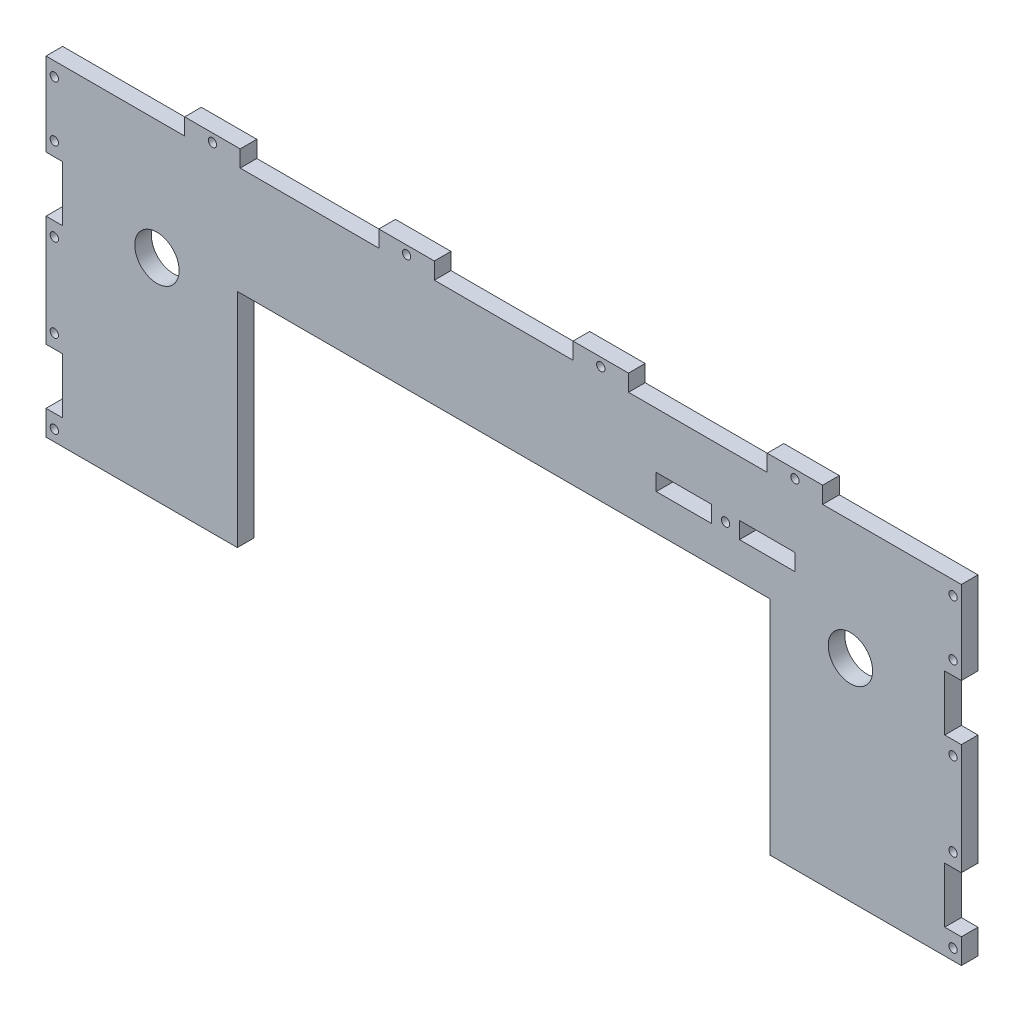
SolidWorks part; units mm, degrees
ref_plane "Plan de face" through (0, 0, 0) normal (0, 0, 1) x (1, 0, 0)
ref_plane "Plan de dessus" through (0, 0, 0) normal (0, 1, 0) x (1, 0, 0)
ref_plane "Plan de droite" through (0, 0, 0) normal (1, 0, 0) x (0, 0, -1)
sketch "Esquisse1" plane through (0, 0, 0) normal (0, 0, 1) x (1, 0, 0)
  line L0 (97.3951, 0) -> (-118.5049, 0) construction
  line L1 (-165, 119) -> (165, 119)
  line L2 (-165, 119) -> (-165, -119)
  line L3 (-165, -119) -> (165, -119)
  line L4 (165, 119) -> (165, -119)
  line L5 (0, 79.3588) -> (0, -79.3588) construction
  line L6 (-92.5, -55) -> (-77.5, -55)
  line L7 (-92.5, -55) -> (-92.5, -61)
  line L8 (-92.5, -61) -> (-77.5, -61)
  line L9 (-77.5, -55) -> (-77.5, -61)
  line L10 (-7.5, -55) -> (7.5, -55)
  line L11 (-7.5, -55) -> (-7.5, -61)
  line L12 (-7.5, -61) -> (7.5, -61)
  line L13 (7.5, -55) -> (7.5, -61)
  line L14 (77.5, -55) -> (92.5, -55)
  line L15 (77.5, -55) -> (77.5, -61)
  line L16 (77.5, -61) -> (92.5, -61)
  line L17 (92.5, -55) -> (92.5, -61)
  line L18 (-225.3679, 76) -> (203.1013, 76) construction
  line L19 (55, 99) -> (75, 99)
  line L20 (55, 99) -> (55, 93)
  line L21 (55, 93) -> (75, 93)
  line L22 (75, 99) -> (75, 93)
  line L23 (85, 99) -> (105, 99)
  line L24 (85, 99) -> (85, 93)
  line L25 (85, 93) -> (105, 93)
  line L26 (105, 99) -> (105, 93)
  circle A0 centre (-125, 76) radius 8
  circle A1 centre (125, 76) radius 8
  dimension "D23" = 16
  dimension "D24" = 16
  dimension "D1" = 238
  dimension "D2" = 330
  dimension "D3" = 165
  dimension "D4" = 119
  dimension "D5" = 15
  dimension "D6" = 6
  dimension "D7" = 6
  dimension "D8" = 15
  dimension "D9" = 6
  dimension "D10" = 15
  dimension "D11" = 70
  dimension "D12" = 70
  dimension "D13" = 58
  dimension "D14" = 72.5
  dimension "D15" = 6
  dimension "D16" = 20
  dimension "D17" = 20
  dimension "D18" = 6
  dimension "D19" = 10
  dimension "D20" = 60
  dimension "D21" = 20
  dimension "D22" = 20
  dimension "D25" = 40
  dimension "D26" = 40
  dimension "D27" = 195
extrude "Boss.-Extru.1" add sketch "Esquisse1" along normal blind 6
sketch "Esquisse2" plane through (0, 0, 6) normal (0, 0, 1) x (1, 0, 0)
  line L0 (243.146, 0) -> (-260.0003, 0) construction
  line L1 (0, 180.4713) -> (0, -129.6072) construction
  line L2 (165, 119) -> (-165, 119) construction
  line L3 (-115, 119) -> (-95, 119)
  line L4 (-115, 119) -> (-115, 125)
  line L5 (-115, 125) -> (-95, 125)
  line L6 (-95, 119) -> (-95, 125)
  line L7 (-165, 119) -> (-165, -119) construction
  line L8 (-45, 119) -> (-25, 119)
  line L9 (-45, 119) -> (-45, 125)
  line L10 (-45, 125) -> (-25, 125)
  line L11 (-25, 119) -> (-25, 125)
  line L12 (25, 119) -> (25, 125)
  line L13 (45, 125) -> (25, 125)
  line L14 (45, 119) -> (45, 125)
  line L15 (45, 119) -> (25, 119)
  line L16 (95, 119) -> (95, 125)
  line L17 (115, 125) -> (95, 125)
  line L18 (115, 119) -> (115, 125)
  line L19 (115, 119) -> (95, 119)
  line L20 (-115, 119) -> (-95, 119)
  line L21 (-115, 119) -> (-115, 125)
  line L22 (-115, 125) -> (-95, 125)
  line L23 (-95, 119) -> (-95, 125)
  line L24 (-45, 119) -> (-25, 119)
  line L25 (-45, 119) -> (-45, 125)
  line L26 (-45, 125) -> (-25, 125)
  line L27 (-25, 119) -> (-25, 125)
  line L28 (25, 119) -> (25, 125)
  line L29 (45, 125) -> (25, 125)
  line L30 (45, 119) -> (45, 125)
  line L31 (45, 119) -> (25, 119)
  line L32 (95, 119) -> (95, 125)
  line L33 (115, 125) -> (95, 125)
  line L34 (115, 119) -> (115, 125)
  line L35 (115, 119) -> (95, 119)
  line L36 (115, -119) -> (95, -119)
  line L37 (115, -119) -> (115, -125)
  line L38 (115, -125) -> (95, -125)
  line L39 (95, -119) -> (95, -125)
  line L40 (45, -119) -> (25, -119)
  line L41 (45, -119) -> (45, -125)
  line L42 (45, -125) -> (25, -125)
  line L43 (25, -119) -> (25, -125)
  line L44 (-25, -119) -> (-25, -125)
  line L45 (-45, -125) -> (-25, -125)
  line L46 (-45, -119) -> (-45, -125)
  line L47 (-45, -119) -> (-25, -119)
  line L48 (-95, -119) -> (-95, -125)
  line L49 (-115, -125) -> (-95, -125)
  line L50 (-115, -119) -> (-115, -125)
  line L51 (-115, -119) -> (-95, -119)
  line L52 (115, -119) -> (95, -119)
  line L53 (115, -119) -> (115, -125)
  line L54 (115, -125) -> (95, -125)
  line L55 (95, -119) -> (95, -125)
  line L56 (45, -119) -> (25, -119)
  line L57 (45, -119) -> (45, -125)
  line L58 (45, -125) -> (25, -125)
  line L59 (25, -119) -> (25, -125)
  line L60 (-25, -119) -> (-25, -125)
  line L61 (-45, -125) -> (-25, -125)
  line L62 (-45, -119) -> (-45, -125)
  line L63 (-45, -119) -> (-25, -119)
  line L64 (-95, -119) -> (-95, -125)
  line L65 (-115, -125) -> (-95, -125)
  line L66 (-115, -119) -> (-115, -125)
  line L67 (-115, -119) -> (-95, -119)
  line M9 (-165, -119) -> (165, -119)
  line M11 (165, 119) -> (-165, 119)
  dimension "D1" = 6
  dimension "D2" = 6
  dimension "D3" = 20
  dimension "D4" = 20
  dimension "D5" = 50
  dimension "D6" = 50
extrude "Boss.-Extru.2" add sketch "Esquisse2" against normal blind 6 contours L6 L5 L4 M11 | L11 L10 L9 M11 | L14 L13 L12 M11 | L18 L17 L16 M11 | L39 L38 L37 M9 | L43 L42 L41 M9 | L46 L45 L44 M9 | L50 L49 L48 M9 region at (-105, 122, 6) region at (105, 122, 6) region at (35, 122, 6) region at (-35, 122, 6) region at (105, -122, 6) region at (-105, -122, 6) region at (-35, -122, 6) region at (35, -122, 6)
sketch "Esquisse3" plane through (0, 0, 6) normal (0, 0, 1) x (1, 0, 0)
  line L0 (-165, 119) -> (-165, -119) construction
  line L1 (-165, 69) -> (-159, 69)
  line L2 (-165, 69) -> (-165, 89)
  line L3 (-165, 89) -> (-159, 89)
  line L4 (-159, 69) -> (-159, 89)
  line L5 (234.1368, 0) -> (-337.9213, 0) construction
  line L6 (-165, 29) -> (-159, 29)
  line L7 (-165, 29) -> (-165, 9)
  line L8 (-165, 9) -> (-159, 9)
  line L9 (-159, 29) -> (-159, 9)
  line L10 (0, 279.7488) -> (0, -188.1201) construction
  line L11 (-115, 119) -> (-165, 119) construction
  line L12 (-159, -29) -> (-159, -9)
  line L13 (-165, -9) -> (-159, -9)
  line L14 (-165, -29) -> (-165, -9)
  line L15 (-165, -29) -> (-159, -29)
  line L16 (-159, -69) -> (-159, -89)
  line L17 (-165, -89) -> (-159, -89)
  line L18 (-165, -69) -> (-165, -89)
  line L19 (-165, -69) -> (-159, -69)
  line L20 (165, -69) -> (159, -69)
  line L21 (165, -69) -> (165, -89)
  line L22 (165, -89) -> (159, -89)
  line L23 (159, -69) -> (159, -89)
  line L24 (165, -29) -> (159, -29)
  line L25 (165, -29) -> (165, -9)
  line L26 (165, -9) -> (159, -9)
  line L27 (159, -29) -> (159, -9)
  line L28 (159, 29) -> (159, 9)
  line L29 (165, 9) -> (159, 9)
  line L30 (165, 29) -> (165, 9)
  line L31 (165, 29) -> (159, 29)
  line L32 (159, 69) -> (159, 89)
  line L33 (165, 89) -> (159, 89)
  line L34 (165, 69) -> (165, 89)
  line L35 (165, 69) -> (159, 69)
  line L36 (153, -119) -> (153, -109)
  line L37 (-165, -119) -> (-153, -119)
  line L38 (-165, -119) -> (-165, -109)
  line L39 (-165, -109) -> (-153, -109)
  line L40 (-153, -119) -> (-153, -109)
  line L41 (165, -109) -> (153, -109)
  line L42 (165, -119) -> (165, -109)
  line L43 (165, -119) -> (153, -119)
  dimension "D1" = 40
  dimension "D2" = 6
  dimension "D3" = 6
  dimension "D4" = 20
  dimension "D5" = 20
  dimension "D6" = 30
  dimension "D7" = 12
  dimension "D8" = 10
extrude "Enlèv. mat.-Extru.1" cut sketch "Esquisse3" against normal blind 6
sketch "Esquisse4" plane through (0, 0, 6) normal (0, 0, 1) x (1, 0, 0)
  line L0 (-162, 122) -> (-162, -131.0602) construction
  line L1 (0, 158.5579) -> (0, -182.4489) construction
  line L2 (-115, 119) -> (-165, 119) construction
  line L3 (-106.4439, -58) -> (117.3944, -58) construction
  line L4 (-159, 89) -> (-165, 89) construction
  line L5 (-165, 119) -> (-165, 89) construction
  line L6 (-165, 69) -> (-159, 69) construction
  line L7 (-159, 29) -> (-165, 29) construction
  line L8 (-165, 9) -> (-159, 9) construction
  line L9 (-159, -9) -> (-165, -9) construction
  line L10 (-92.5, -55) -> (-92.5, -61) construction
  line L11 (-77.5, -61) -> (-77.5, -55) construction
  line L12 (-165, -29) -> (-159, -29) construction
  line L13 (-159, -69) -> (-165, -69) construction
  line L14 (-165, -89) -> (-159, -89) construction
  line L15 (-7.5, -55) -> (-7.5, -61) construction
  line L16 (162, 122) -> (162, -131.0602) construction
  line L17 (116.5184, 96) -> (43.4816, 96) construction
  line L18 (-126.5544, 122) -> (2.7821, 122) construction
  line L19 (-45, 119) -> (-95, 119) construction
  line L20 (-45, 119) -> (-45, 125) construction
  line L21 (75, 93) -> (75, 99) construction
  line L23 (55, 93) -> (75, 93) construction
  circle A0 centre (-162, 114) radius 1.5
  circle A1 centre (-162, 94) radius 1.5
  circle A2 centre (-162, 64) radius 1.5
  circle A3 centre (-162, 34) radius 1.5
  circle A4 centre (-162, 4) radius 1.5
  circle A5 centre (-105, 122) radius 1.5
  circle A6 centre (-162, -4) radius 1.5
  circle A7 centre (-162, -34) radius 1.5
  circle A8 centre (-162, -64) radius 1.5
  circle A9 centre (-162, -94) radius 1.5
  circle A10 centre (-97.5, -58) radius 1.5
  circle A11 centre (-72.5, -58) radius 1.5
  circle A12 centre (162, -94) radius 1.5
  circle A13 centre (162, -64) radius 1.5
  circle A14 centre (162, -34) radius 1.5
  circle A15 centre (162, -4) radius 1.5
  circle A16 centre (80, 96) radius 1.5
  circle A17 centre (162, 4) radius 1.5
  circle A18 centre (162, 34) radius 1.5
  circle A19 centre (162, 64) radius 1.5
  circle A20 centre (162, 94) radius 1.5
  circle A21 centre (162, 114) radius 1.5
  circle A22 centre (-12.5, -58) radius 1.5
  circle A23 centre (12.5, -58) radius 1.5
  circle A24 centre (72.5, -58) radius 1.5
  circle A25 centre (97.5, -58) radius 1.5
  circle A26 centre (-35, 122) radius 1.5
  circle A27 centre (35, 122) radius 1.5
  circle A28 centre (105, 122) radius 1.5
  dimension "D1" = 3
  dimension "D2" = 3
  dimension "D3" = 3
  dimension "D4" = 3
  dimension "D5" = 3
  dimension "D6" = 3
  dimension "D7" = 3
  dimension "D8" = 3
  dimension "D9" = 3
  dimension "D10" = 3
  dimension "D11" = 3
  dimension "D12" = 5
  dimension "D13" = 5
  dimension "D15" = 5
  dimension "D16" = 5
  dimension "D17" = 5
  dimension "D19" = 3
  dimension "D20" = 5
  dimension "D21" = 5
  dimension "D23" = 3
  dimension "D24" = 3
  dimension "D25" = 5
  dimension "D26" = 5
  dimension "D27" = 5
  dimension "D28" = 10
  dimension "D29" = 3
  dimension "D30" = 5
  dimension "D31" = 3
  dimension "D33" = 10
  dimension "D14" = 3
  dimension "D18" = 5
  dimension "D22" = 5
  dimension "D32" = 3
extrude "Enlèv. mat.-Extru.2" cut sketch "Esquisse4" against normal blind 6
sketch "Esquisse5" plane through (0, 0, 6) normal (0, 0, 1) x (1, 0, 0)
  line L1 (-200.0968, 0) -> (223.5072, 0)
  line L2 (-200.0968, 0) -> (-200.0968, -150.3561)
  line L3 (-200.0968, -150.3561) -> (223.5072, -150.3561)
  line L4 (223.5072, 0) -> (223.5072, -150.3561)
extrude "Enlèv. mat.-Extru.3" cut sketch "Esquisse5" against normal blind 6
sketch "Esquisse6" plane through (0, 0, 6) normal (0, 0, 1) x (1, 0, 0)
  line L0 (-165, 69) -> (-165, 29) construction
  line L2 (165, 0) -> (-165, 0) construction
  text T0 "SUDRIABOTIK" font "Century Gothic" height in points 72
  dimension "D1" = 83.5
  dimension "D2" = 29.5
extrude "Enlèv. mat.-Extru.4" cut sketch "Esquisse6" against normal blind 6
sketch "Esquisse7" plane through (0, 0, 6) normal (0, 0, 1) x (1, 0, 0)
  line L0 (-42.8696, 29.5) -> (-48.7731, 29.5) construction
  line L1 (-44.3875, 29.5) -> (-45.9701, 29.5)
  line L2 (-44.3875, 29.5) -> (-44.3875, 31.4538)
  line L3 (-44.3875, 31.4538) -> (-45.9701, 31.4538)
  line L4 (-45.9701, 29.5) -> (-45.9701, 31.4538)
  line L5 (-47.0635, 31.4538) -> (-44.8768, 31.4538) construction
  line L6 (-23.9531, 46.5962) -> (-27.525, 46.5962) construction
  line L7 (-45.1788, 46.5937) -> (-43.5909, 46.5937)
  line L8 (-45.1788, 46.5937) -> (-45.1788, 48.5305)
  line L9 (-45.1788, 48.5305) -> (-43.5909, 48.5305)
  line L10 (-43.5909, 46.5937) -> (-43.5909, 48.5305)
  line L11 (-26.3286, 46.5962) -> (-25.4223, 46.5962)
  line L12 (-26.3286, 46.5962) -> (-26.3286, 48.55)
  line L13 (-26.3286, 48.55) -> (-25.4223, 48.55)
  line L14 (-25.4223, 46.5962) -> (-25.4223, 48.55)
  line L15 (-27.525, 46.5962) -> (-27.525, 40.2462) construction
  line L16 (-27.525, 43.4212) -> (-29.2346, 43.4212)
  line L17 (-27.525, 43.4212) -> (-27.525, 42.4505)
  line L18 (-27.525, 42.4505) -> (-29.2346, 42.4505)
  line L19 (-29.2346, 43.4212) -> (-29.2346, 42.4505)
  line L20 (-29.2346, 29.5) -> (-29.2346, 48.55) construction
  line L21 (-2.2967, 37.5596) -> (4.5112, 37.5596) construction
  line L22 (0.6712, 37.5596) -> (1.8879, 37.5596)
  line L23 (0.6712, 37.5596) -> (0.6712, 35.6058)
  line L24 (0.6712, 35.6058) -> (1.8879, 35.6058)
  line L25 (1.8879, 37.5596) -> (1.8879, 35.6058)
  line L26 (5.4118, 35.6058) -> (-3.224, 35.6058) construction
  line L27 (15.2154, 46.5962) -> (15.2154, 40.4904) construction
  line L28 (15.2154, 43.5433) -> (13.5058, 43.5433)
  line L29 (15.2154, 43.5433) -> (15.2154, 40.4904)
  line L30 (15.2154, 40.4904) -> (13.5058, 40.4904)
  line L31 (13.5058, 43.5433) -> (13.5058, 40.4904)
  line L32 (13.5058, 29.5) -> (13.5058, 48.55) construction
  line L33 (15.2154, 38.5365) -> (15.2154, 31.4538) construction
  line L34 (15.2154, 32.964) -> (13.5058, 32.964)
  line L35 (15.2154, 32.964) -> (15.2154, 35.6058)
  line L36 (15.2154, 35.6058) -> (13.5058, 35.6058)
  line L37 (13.5058, 32.964) -> (13.5058, 35.6058)
  line L39 (29.3929, 39.4529) -> (27.6822, 39.4529)
  line L40 (29.3929, 39.4529) -> (29.3929, 38.5462)
  line L41 (29.3929, 38.5462) -> (27.6822, 38.5462)
  line L42 (27.6822, 39.4529) -> (27.6822, 38.5462)
  line L43 (45.9733, 39.5873) -> (47.6814, 39.5873)
  line L44 (45.9733, 39.5873) -> (45.9733, 38.4818)
  line L45 (45.9733, 38.4818) -> (47.6814, 38.4818)
  line L46 (47.6814, 39.5873) -> (47.6814, 38.4818)
  spline S0 degree 3 poles (-39.8701, 46.0619) (-40.0299, 46.1061) (-40.3695, 46.2) (-40.9238, 46.3025) (-41.5477, 46.3928) (-42.2438, 46.4694) (-43.0115, 46.5243) (-43.8512, 46.5655) (-44.7634, 46.5933) (-45.3958, 46.5952) (-45.724, 46.5962) knots 0 0 0 0 0.084319 0.179285 0.286583 0.405111 0.535593 0.67819 0.832976 1 1 1 1 construction
  spline S1 degree 3 poles (-44.9264, 48.55) (-44.5919, 48.5476) (-43.9455, 48.5429) (-43.0114, 48.5134) (-42.1472, 48.4612) (-41.3556, 48.3852) (-40.6345, 48.2918) (-39.986, 48.1748) (-39.4066, 48.0366) (-39.0502, 47.9188) (-38.8817, 47.8631) knots 0 0 0 0 0.164289 0.317406 0.458844 0.589367 0.707831 0.81577 0.91288 1 1 1 1 construction
  spline S2 degree 3 poles (37.6465, 47.0846) (37.4657, 47.0824) (37.1058, 47.078) (36.5709, 47.0202) (36.043, 46.9379) (35.522, 46.8204) (35.0101, 46.6604) (34.5026, 46.4762) (34.004, 46.2518) (33.516, 45.9983) (33.0429, 45.7178) (32.5966, 45.4077) (32.1757, 45.0754) (31.7814, 44.72) (31.4148, 44.3398) (31.0687, 43.9406) (30.757, 43.5108) (30.4714, 43.0623) (30.2157, 42.5955) (29.9884, 42.1154) (29.8024, 41.618) (29.6508, 41.1088) (29.5251, 40.5886) (29.4454, 40.0534) (29.387, 39.5058) (29.3829, 39.1358) (29.3808, 38.9487) knots 0 0 0 0 0.042023 0.083645 0.124984 0.166247 0.207702 0.249631 0.291742 0.334743 0.37746 0.419556 0.461044 0.502096 0.542891 0.583801 0.624864 0.666225 0.707399 0.748557 0.789655 0.83074 0.87207 0.913993 0.956498 1 1 1 1 construction
  spline S3 degree 3 poles (37.7151, 29.0115) (37.3699, 29.02) (36.6894, 29.0366) (35.6905, 29.1791) (34.731, 29.4019) (33.8138, 29.7204) (32.9384, 30.132) (32.1029, 30.6338) (31.3109, 31.2293) (30.5688, 31.9051) (29.8898, 32.6409) (29.2979, 33.4292) (28.7959, 34.2546) (28.3857, 35.1195) (28.0609, 36.0196) (27.8394, 36.9609) (27.6961, 37.9381) (27.6795, 38.6034) (27.6712, 38.941) knots 0 0 0 0 0.065819 0.129747 0.192072 0.253459 0.31457 0.37628 0.439026 0.503267 0.567493 0.629705 0.691 0.751452 0.812004 0.87315 0.935635 1 1 1 1 construction
  spline S4 degree 3 poles (45.9885, 39.0364) (45.9863, 39.221) (45.9819, 39.5872) (45.9246, 40.1286) (45.8424, 40.6579) (45.7239, 41.1732) (45.5713, 41.6744) (45.383, 42.1613) (45.161, 42.6355) (44.9062, 43.0959) (44.6199, 43.5378) (44.3069, 43.9601) (43.962, 44.3551) (43.595, 44.7325) (43.1968, 45.0842) (42.7691, 45.4104) (42.3171, 45.7188) (41.8385, 45.9971) (41.3446, 46.2541) (40.8378, 46.4743) (40.3238, 46.6613) (39.804, 46.8209) (39.274, 46.9374) (38.7373, 47.0203) (38.1947, 47.078) (37.8298, 47.0824) (37.6465, 47.0846) knots 0 0 0 0 0.042915 0.08513 0.126473 0.167453 0.207976 0.248249 0.28875 0.32967 0.370537 0.411129 0.451819 0.492406 0.533486 0.575263 0.617441 0.660672 0.70394 0.746868 0.789079 0.831104 0.873238 0.915166 0.957381 1 1 1 1 construction
  spline S5 degree 3 poles (47.6981, 39.0326) (47.6896, 38.69) (47.673, 38.0145) (47.5306, 37.0231) (47.3072, 36.0702) (46.9883, 35.1571) (46.5788, 34.2831) (46.0745, 33.4504) (45.4805, 32.6588) (44.8044, 31.9169) (44.0675, 31.2365) (43.277, 30.6437) (42.4508, 30.1336) (41.5783, 29.7265) (40.6709, 29.4012) (39.7207, 29.1794) (38.732, 29.0363) (38.0578, 29.0199) (37.7151, 29.0115) knots 0 0 0 0 0.065227 0.128569 0.19032 0.251378 0.312388 0.373789 0.436431 0.500567 0.564687 0.627136 0.688455 0.749246 0.810155 0.871671 0.934773 1 1 1 1 construction
  spline S6 degree 3 poles (29.3808, 38.9487) (29.3877, 38.6735) (29.4014, 38.1321) (29.5209, 37.3387) (29.705, 36.5762) (29.9763, 35.8488) (30.3157, 35.1502) (30.7349, 34.4867) (31.2316, 33.858) (31.7959, 33.2686) (32.4127, 32.7306) (33.0676, 32.2584) (33.7537, 31.8588) (34.4727, 31.5333) (35.2208, 31.2753) (36.0029, 31.0986) (36.8136, 30.9822) (37.3662, 30.9711) (37.6465, 30.9654) knots 0 0 0 0 0.064504 0.126899 0.187747 0.24815 0.308586 0.369583 0.431827 0.49618 0.560668 0.623504 0.68526 0.746537 0.808327 0.870486 0.934317 1 1 1 1 construction
  spline S7 degree 3 poles (37.6465, 30.9654) (37.8348, 30.968) (38.2084, 30.9731) (38.7641, 31.0248) (39.3098, 31.1077) (39.8447, 31.2271) (40.3682, 31.3765) (40.8825, 31.5539) (41.3822, 31.7754) (41.8735, 32.02) (42.3437, 32.2989) (42.7926, 32.5985) (43.2089, 32.9303) (43.6029, 33.2804) (43.9709, 33.6557) (44.3106, 34.0559) (44.6208, 34.4834) (44.9063, 34.9313) (45.1611, 35.3993) (45.383, 35.8812) (45.5713, 36.3756) (45.7233, 36.8834) (45.8425, 37.4035) (45.9245, 37.9367) (45.982, 38.4819) (45.9863, 38.8506) (45.9885, 39.0364) knots 0 0 0 0 0.043633 0.086538 0.129177 0.171436 0.213416 0.255266 0.297369 0.339941 0.382347 0.423953 0.464871 0.505572 0.546003 0.586568 0.627065 0.668271 0.709549 0.750428 0.791096 0.832027 0.873136 0.914611 0.956956 1 1 1 1 construction
extrude "Boss.-Extru.5" add sketch "Esquisse7" against normal blind 6
sketch "Esquisse8" plane through (0, 0, 6) normal (0, 0, 1) x (1, 0, 0)
  line L0 (165, 0) -> (-165, 0) construction
  line L1 (-96.0144, 0) -> (96.0356, 0)
  line L2 (-96.0144, 0) -> (-96.0144, 80)
  line L3 (-96.0144, 80) -> (96.0356, 80)
  line L4 (96.0356, 0) -> (96.0356, 80)
  dimension "D1" = 192.05
  dimension "D2" = 80
  dimension "D3" = 15
extrude "Enlèv. mat.-Extru.5" cut sketch "Esquisse8" against normal blind 6 contours L2 L3 L4 L1
equation "\"D3@Esquisse1\"=\"D2@Esquisse1\"/2"
equation "\"D4@Esquisse1\"=\"D1@Esquisse1\"/2"
